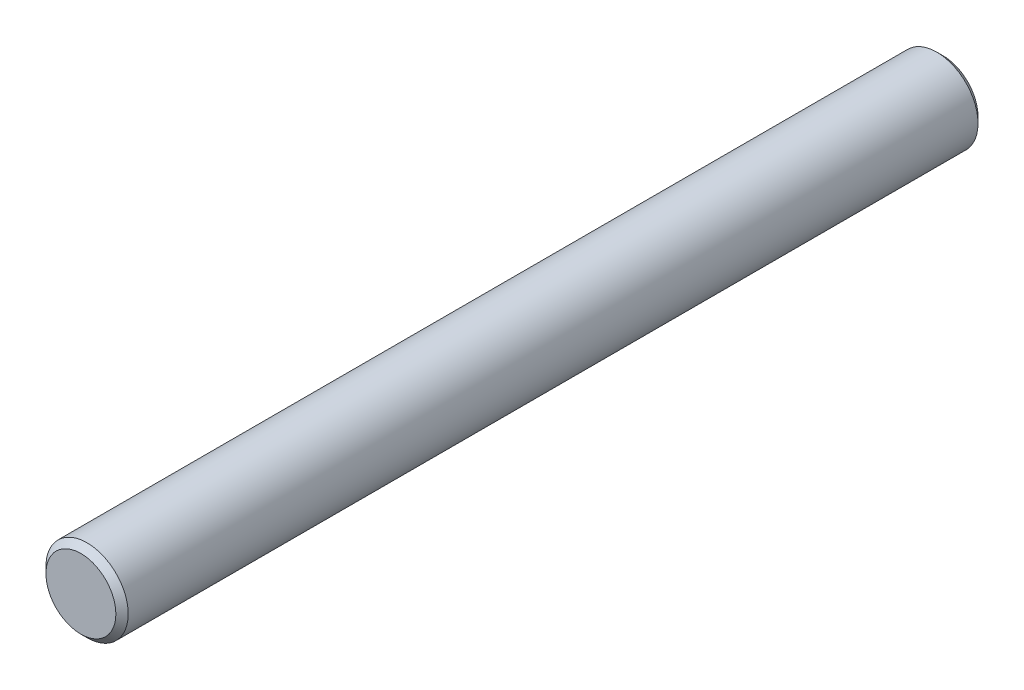
SolidWorks part; units mm, degrees
ref_plane "Front Plane" through (0, 0, 0) normal (0, 0, 1) x (1, 0, 0)
ref_plane "Top Plane" through (0, 0, 0) normal (0, 1, 0) x (1, 0, 0)
ref_plane "Right Plane" through (0, 0, 0) normal (1, 0, 0) x (0, 0, -1)
sketch "Sketch1" plane through (0, 0, 0) normal (1, 0, 0) x (0, 0, -1)
  line L0 (41.5925, 0) -> (-41.5925, 0) construction
  line L1 (-41.5925, -3.9688) -> (-41.5925, 3.9687) construction
  line L2 (-41.5925, 3.9687) -> (-43.0036, 3.9687) construction
  line L3 (41.5925, 3.9687) -> (41.5925, -3.9687) construction
  point P3 (41.5925, 3.9687)
  point P4 (0, 0)
  point P7 (-41.5925, 0)
  point P8 (-38.0647, -3.9688)
  point P12 (-29.6862, 3.9687)
  point P13 (41.5925, 0)
  point P15 (29.6862, 3.9688)
  point P19 (58.5964, -3.9688)
  dimension "OD" = 7.9375
  dimension "Pitch" = 1.4111
  dimension "Length" = 83.185
  dimension "D1" = 3.5278
  dimension "D4" = 11.9062
  dimension "D5" = 11.9062
  dimension "SL" = 100.1889
sketch "Sketch2" plane through (0, 0, 0) normal (0, 0, 1) x (1, 0, 0)
  line L0 (0, -3.9688) -> (0, 3.9687) construction
  line L1 (-3.9687, 0) -> (3.9687, 0) construction
  circle A0 centre (0, 0) radius 3.9687
extrude "Boss-Extrude1" add sketch "Sketch2" along normal up to vertex (41.5925 mm away) and the other way up to vertex (41.5925 mm away) up to point (0, 0, 41.5925) other way up to point (0, 0, -41.5925)
chamfer "Chamfer1" distance 0.5953 angle 45 2 edges at (3.9687, 0, -41.5925) (3.9687, 0, 41.5925)
ref_axis "Center Axis 1" through (0, 0, -41.5925) along (0, 0, 1)
sketch "Sketch13" [suppressed] plane through (0, 0, 304.8) normal (0, 0, 1) x (1, 0, 0)
  circle A0 centre (0, 0) radius 3.9687
curve "Helix/Spiral1" [suppressed] pitch 1.4111 height 101.6 turns 72
sketch "Sketch14" [suppressed] plane through (0, 0, 0) normal (1, 0, 0) x (0, 0, -1)
  line L0 (-306.1229, 4.1215) -> (-305.4174, 2.8994) construction
  line L1 (-305.4174, 2.8994) -> (-304.7118, 4.1215) construction
  line L2 (-304.7118, 4.1215) -> (-306.1229, 4.1215) construction
  line L3 (-305.4174, 4.1215) -> (-305.4174, 3.9687) construction
  line L4 (-305.4174, 3.9687) -> (-305.4174, 3.0522) construction
  line L5 (-305.4174, 3.0522) -> (-305.4174, 2.8994) construction
  line L6 (-306.0347, 3.9687) -> (-304.8, 3.9687) construction
  line L8 (-304.7559, 4.0451) -> (-306.0788, 4.0451) construction
  line L9 (-305.5056, 3.0522) -> (-305.3292, 3.0522)
  line L10 (-305.5056, 3.0522) -> (-305.3292, 3.0522) construction
  line L11 (-305.3292, 3.0522) -> (-304.7559, 4.0451)
  line L12 (-304.7559, 4.0451) -> (-306.0788, 4.0451)
  line L13 (-306.0788, 4.0451) -> (-305.5056, 3.0522)
  point P9 (-305.4174, 3.0522)
  point P14 (-305.4174, 3.9687)
  point P16 (-305.4174, 4.0451)
  point P17 (-305.4174, 4.0451)
  dimension "D1" = 1.4111
  dimension "D2" = 0.1764
sweep "Cut-Sweep1" [suppressed] cut profiles "Sketch14" path "Helix/Spiral1"
pattern_linear "LPattern1" [suppressed] count 7 spacing 100.1889 along (0, 0, -1) of bodies 503
ref_axis "Axis1" through (0, 0, 335.28) along (0, 0, -1)
equation "\"D1@Chamfer1\"=\"OD@Sketch1\"*.075"
equation "\"D4@Sketch1\"=\"OD@Sketch1\"*1.5"
equation "\"D5@Sketch1\"=\"OD@Sketch1\"*1.5"
equation "\"SL@Sketch1\"=\"Pitch@Sketch1\"*71"
equation "\"D4@Helix/Spiral1\"=\"Pitch@Sketch1\""
equation "\"D5@Helix/Spiral1\"= ( \"SL@Sketch1\" / \"Pitch@Sketch1\" ) + 1"
equation "\"D1@Sketch14\"=\"Pitch@Sketch1\""
equation "\"D2@Sketch14\"=\"D1@Sketch14\"/8"
equation "\"D3@LPattern1\"=\"SL@Sketch1\""
equation "\"D1@Sketch1\"=\"Pitch@Sketch1\"*2.5"
